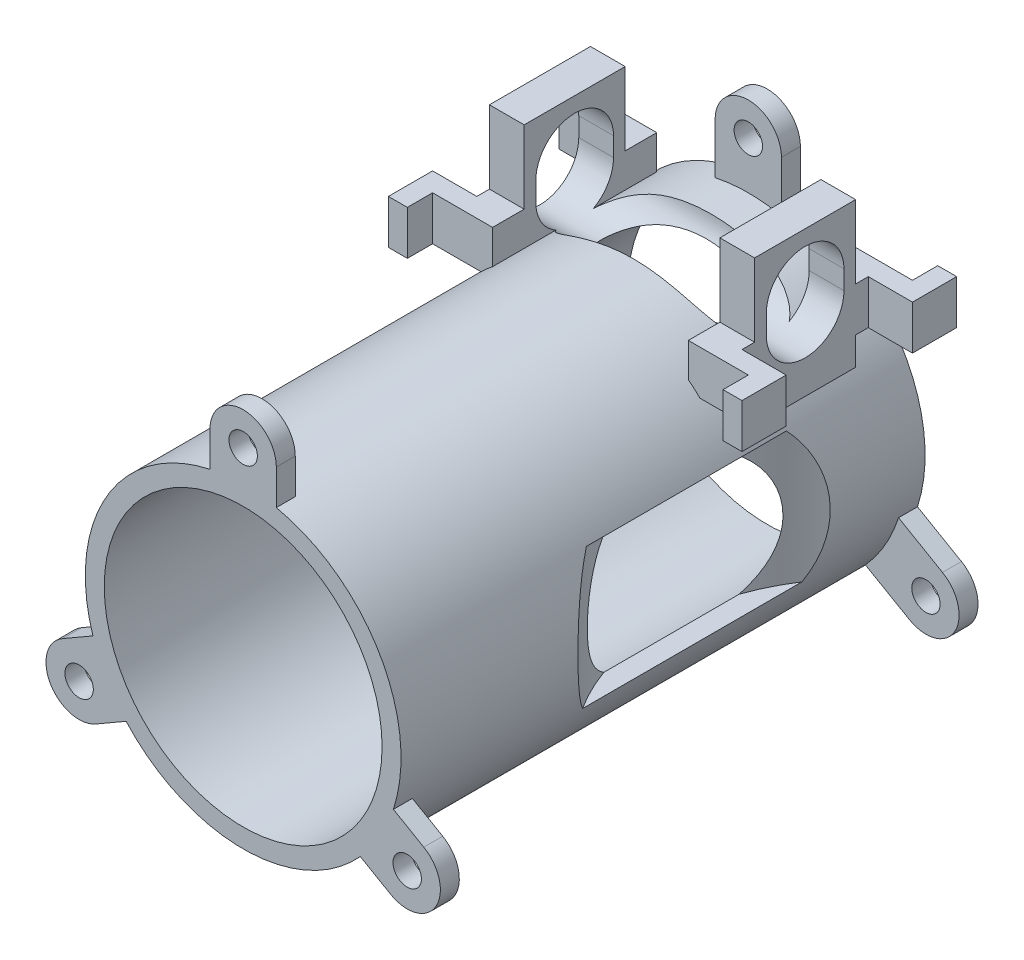
SolidWorks part; units mm, degrees
ref_plane "Front Plane" through (0, 0, 0) normal (0, 0, 1) x (1, 0, 0)
ref_plane "Top Plane" through (0, 0, 0) normal (0, 1, 0) x (1, 0, 0)
ref_plane "Right Plane" through (0, 0, 0) normal (1, 0, 0) x (0, 0, -1)
sketch "Sketch1" plane through (0, 0, 0) normal (0, 0, 1) x (1, 0, 0)
  circle A0 centre (0, 0) radius 22
  circle A1 centre (0, 0) radius 25
  dimension "D1" = 44
  dimension "D2" = 3
extrude "Boss-Extrude1" add sketch "Sketch1" along normal blind 30
ref_plane "Plane1" through (0, 0, 15) normal (0, 0, 1) x (1, 0, 0)
sketch "Sketch3" plane through (0, 0, 0) normal (1, 0, 0) x (0, 0, -1)
  line L0 (0, 25) -> (-30, 25) construction
  circle A0 centre (-15, 25) radius 6.15
  dimension "D1" = 12.3
extrude "Cut-Extrude1" cut sketch "Sketch3" against normal mid plane 50
sketch "Sketch7" plane through (0, 0, 30) normal (0, 0, 1) x (1, 0, 0)
  circle A0 centre (0, 0) radius 22
  circle A1 centre (0, 0) radius 25
extrude "Boss-Extrude4" add sketch "Sketch7" along normal blind 53
ref_plane "Plane2" through (-25, 0, 0) normal (-1, 0, 0) x (0, 0, 1)
sketch "Sketch9" plane through (0, 0, 0) normal (0, 0, -1) x (-1, 0, 0)
  line L0 (0, 0) -> (0, 32.4847) construction
  line L1 (-5.25, 32.4847) -> (-5.25, 24.4425)
  line L2 (5.25, 32.4847) -> (5.25, 24.4425)
  circle A0 centre (0, 32.4847) radius 2.25
  circle A1 centre (0, 32.4847) radius 5.25
  circle A2 centre (0, 0) radius 25 construction
  arc A3 (-5.25, 24.4425) -> (5.25, 24.4425) centre (0, 0) cw
  circle M3 centre (0, 0) radius 25
  dimension "D1" = 4.5
  dimension "D2" = 3
extrude "Boss-Extrude5" add sketch "Sketch9" against normal blind 3 contours A1 L1 M3 | A1 A3 A0 M3 | A1 L2 M3 region at (0, 26.7779, 0) region at (0, 37.5862, 0)
pattern_circular "CirPattern1" count 3 over 360 about axis through (0, 0, 0) along (0, 0, 1) of "Boss-Extrude5"
sketch "Sketch10" plane through (0, 0, 83) normal (0, 0, 1) x (1, 0, 0)
  line L0 (-5.25, 30) -> (-5.25, 24.4425)
  line L1 (5.25, 30) -> (5.25, 24.4425)
  line L2 (0, 0) -> (0, 30) construction
  circle A0 centre (0, 30) radius 2.25
  circle A1 centre (0, 30) radius 5.25
  arc A2 (-5.25, 24.4425) -> (5.25, 24.4425) centre (0, 0) cw
  circle A3 centre (0, 0) radius 25 construction
  circle M5 centre (0, 0) radius 25
  dimension "D2" = 4.5
  dimension "D3" = 30
  dimension "D1" = 3
extrude "Boss-Extrude6" add sketch "Sketch10" against normal blind 3 contours A1 A0 M5 | A1 L0 M5 | A1 L1 M5 region at (-4.234, 25.9338, 83) region at (0, 35.103, 83) region at (4.234, 25.9338, 83)
pattern_circular "CirPattern2" count 3 every 120 about axis through (0, 0, 83) along (0, 0, 1) of "Boss-Extrude6"
ref_plane "Plane3" through (0, 11.51, 0) normal (0, 1, 0) x (1, 0, 0)
sketch "Sketch14" plane through (0, 0, 15) normal (0, 0, 1) x (1, 0, 0)
  line L0 (-21, 13.5647) -> (-21, 36.5647)
  line L1 (-21, 36.5647) -> (-15.5, 36.5647)
  line L2 (-15.5, 36.5647) -> (-15.5, 19.615)
  line L3 (-25, 27.5) -> (-25, -27.5) construction
  arc A0 (-5.25, 24.4425) -> (-23.7929, -7.6746) centre (0, 0) ccw construction
  arc A1 (-15.5, 19.615) -> (-21, 13.5647) centre (0, 0) ccw
  dimension "D1" = 23
  dimension "D2" = 4
  dimension "D3" = 5.5
extrude "Boss-Extrude7" add sketch "Sketch14" along normal mid plane 16
sketch "Sketch15" plane through (-21, 0, 0) normal (-1, 0, 0) x (0, 0, 1)
  line L0 (15, 25) -> (15, 28) construction
  line L1 (15, -27.5) -> (15, 27.5) construction
  line L2 (8.85, 25) -> (8.85, 28)
  line L3 (21.15, 25) -> (21.15, 28)
  line L4 (80, 25) -> (21.15, 25) construction
  arc A0 (8.85, 25) -> (21.15, 25) centre (15, 25) ccw
  arc A1 (21.15, 28) -> (8.85, 28) centre (15, 28) ccw
  point P4 (15, 26.5)
  dimension "D1" = 6.15
  dimension "D2" = 3
extrude "Cut-Extrude5" cut sketch "Sketch15" against normal blind 16
ref_plane "Plane5" through (0, 25, 0) normal (0, 1, 0) x (1, 0, 0)
sketch "Sketch17" plane through (0, 25, 0) normal (0, 1, 0) x (1, 0, 0)
  line L1 (-15.5, -23) -> (-21, -23)
  line L2 (-15.5, -23) -> (-15.5, -25)
  line L3 (-15.5, -25) -> (-21, -25)
  line L4 (-21, -23) -> (-21, -25)
  line L5 (-15.5, -23) -> (-21, -25) construction
  line L6 (-15.5, -25) -> (-21, -23) construction
  line L7 (-15.5, -25) -> (-28, -25)
  line L8 (-15.5, -25) -> (-15.5, -28)
  line L9 (-15.5, -28) -> (-28, -28)
  line L10 (-28, -25) -> (-28, -28)
  line L11 (-15.5, -25) -> (-28, -28) construction
  line L12 (-15.5, -28) -> (-28, -25) construction
  line L13 (-28, -28) -> (-25, -28)
  line L14 (-28, -28) -> (-28, -32)
  line L15 (-28, -32) -> (-25, -32)
  line L16 (-25, -28) -> (-25, -32)
  line L17 (-28, -28) -> (-25, -32) construction
  line L18 (-28, -32) -> (-25, -28) construction
  point P4 (-18.25, -24)
  point P10 (-21.75, -26.5)
  point P14 (-26.5, -30)
  dimension "D1" = 2
  dimension "D2" = 3
  dimension "D3" = 4
  dimension "D4" = 4
extrude "Boss-Extrude8" add sketch "Sketch17" against normal blind 7 contours L16 L9 L14 L15 | L7 L10 L9 L8 L3 | L1 L4 L3 L2 region at (-18.25, 25, 24) region at (-21.75, 25, 26.5) region at (-26.5, 25, 30)
mirror "Mirror1" about plane through (0, 0, 15) normal (0, 0, 1) of "Boss-Extrude8"
mirror "Mirror2" about plane through (0, 0, 0) normal (1, 0, 0) of "Mirror1", "Boss-Extrude8", "Cut-Extrude5", "Boss-Extrude7"
sketch "Sketch12" plane through (0, 11.51, 0) normal (0, 1, 0) x (1, 0, 0)
  line L0 (0, -44.5194) -> (0, -33.7673) construction
  line L1 (-25.5075, 0) -> (-33.3825, 0) construction
  circle A0 centre (-50, -35) radius 30
  circle A1 centre (50, -35) radius 30
  circle A2 centre (-50, -35) radius 32
  circle A3 centre (50, -35) radius 32
  dimension "D1" = 60
  dimension "D2" = 100
  dimension "D3" = 35
  dimension "D4" = 2
extrude "Cut-Extrude4" cut sketch "Sketch12" against normal blind 21 contours A2 A0 | A1 | A3 A1 | A0 region at (50, 11.51, 35) region at (-81.0949, 11.51, 35) region at (18.9051, 11.51, 35)
